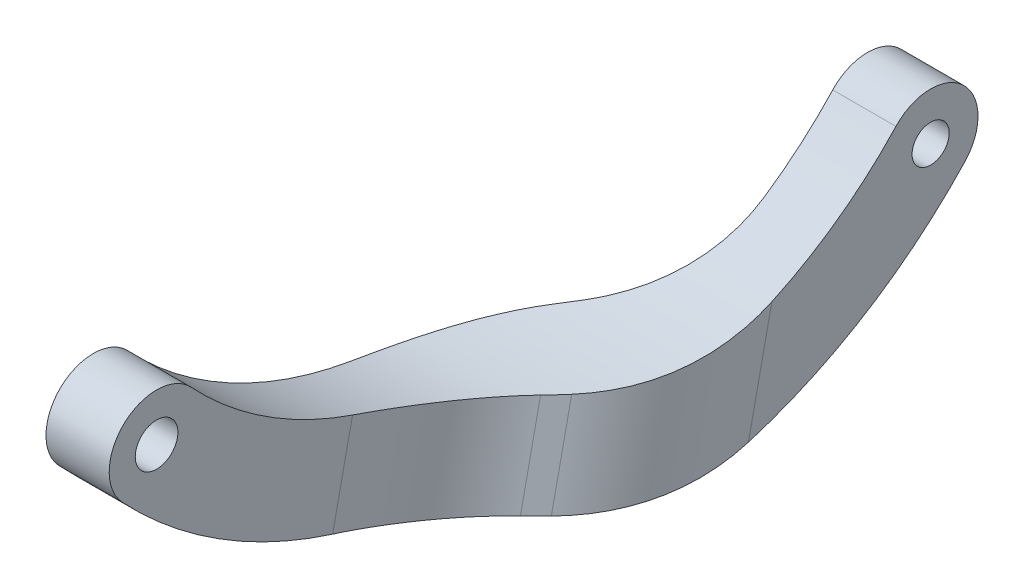
SolidWorks part; units mm, degrees
material "环氧树脂,未充填"
ref_plane "前视基准面" through (0, 0, 0) normal (0, 0, 1) x (1, 0, 0)
ref_plane "上视基准面" through (0, 0, 0) normal (0, 1, 0) x (1, 0, 0)
ref_plane "右视基准面" through (0, 0, 0) normal (1, 0, 0) x (0, 0, -1)
other "Configuration Table"
sketch "草图1" plane through (0, 0, 0) normal (1, 0, 0) x (0, 0, -1)
  line L0 (-20.5, 0) -> (20.5, 0) construction
  line L1 (-20.5, 0) -> (20.5, 0) construction
  line L2 (-20.5, 3) -> (20.5, 3) construction
  line L3 (-20.5, -3) -> (20.5, -3) construction
  line L4 (0, 19.0722) -> (-6.4804, -11.2429) construction
  line L5 (-20.5, 0) -> (0, 19.0722) construction
  line L6 (-6.4804, -11.2429) -> (-5.2261, -5.3754)
  line L7 (0, 19.0722) -> (14.1057, -8.5327) construction
  line L8 (14.1057, -8.5327) -> (11.3755, -3.1898)
  line L9 (20.5, 0) -> (0, 19.0722) construction
  circle A0 centre (20.5, 0) radius 1.175
  circle A1 centre (-20.5, 0) radius 1.35
  arc A2 (-20.5, 3) -> (-20.5, -3) centre (-20.5, 0) ccw construction
  arc A3 (20.5, -3) -> (20.5, 3) centre (20.5, 0) ccw construction
  arc A4 (-20.5, 0) -> (20.5, 0) centre (0, 19.0722) ccw construction
  arc A9 (-22.6964, -2.0435) -> (22.6964, -2.0435) centre (0, 19.0722) ccw
  arc A10 (-18.3036, 2.0435) -> (18.3036, 2.0435) centre (0, 19.0722) ccw
  arc A11 (-18.3036, 2.0435) -> (-22.6964, -2.0435) centre (-20.5, 0) ccw
  arc A12 (22.6964, -2.0435) -> (18.3036, 2.0435) centre (20.5, 0) ccw
  point P4 (0, 0)
  point P8 (0, 0)
  point P15 (0, -8.9278)
  dimension "D1" = 2.35
  dimension "D3" = 3
  dimension "D4" = 3
  dimension "D5" = 25
  dimension "D6" = 2.7
  dimension "D2" = 41
  dimension "D7" = 35
  dimension "D8" = 20
extrude "凸台-拉伸1" add sketch "草图1" along normal blind 4 contours A10 A11 A9 L6 A1 | A9 A12 A10 L6 A0 | A10 L6 A9 L8 region at (0, -4.4994, 14.2833) region at (0, -8.256, -3.5978) region at (0, -2.5851, -17.5564)
extrude "凸台-拉伸2" add sketch "草图1<5>" along normal blind 12 contours A10 L6 A9 L8 | A9 A12 A10 L8 A0 region at (0, -8.256, -3.5978) region at (0, -2.5851, -17.5564)
sketch "草图1<5>" plane through (0, 0, 0) normal (1, 0, 0) x (0, 0, -1) same geometry as "草图1"
extrude "切除-拉伸1" cut sketch "草图1<6>" along normal blind 8 contours A9 A12 A10 L8 A0 region at (0, -2.5851, -17.5564)
sketch "草图1<6>" plane through (0, 0, 0) normal (1, 0, 0) x (0, 0, -1) same geometry as "草图1"
sketch "草图3" plane through (0, 0, 0) normal (-1, 0, 0) x (0, 0, 1)
  circle A0 centre (20.5, 0) radius 1.625
  dimension "D1" = 3.25
extrude "切除-拉伸2" cut sketch "草图3" against normal blind 1
chamfer "倒角1" distance 10 angle 45 2 edges at (12, -8.3091, 5.8532) (0, -5.8612, -12.7406)
fillet "圆角1" radius 12 4 edges at (12, -8.5688, -4.3172) (8, -6.7068, -10.9267) (4, -8.6565, 3.8823) (0, -8.7443, -2.9839)
